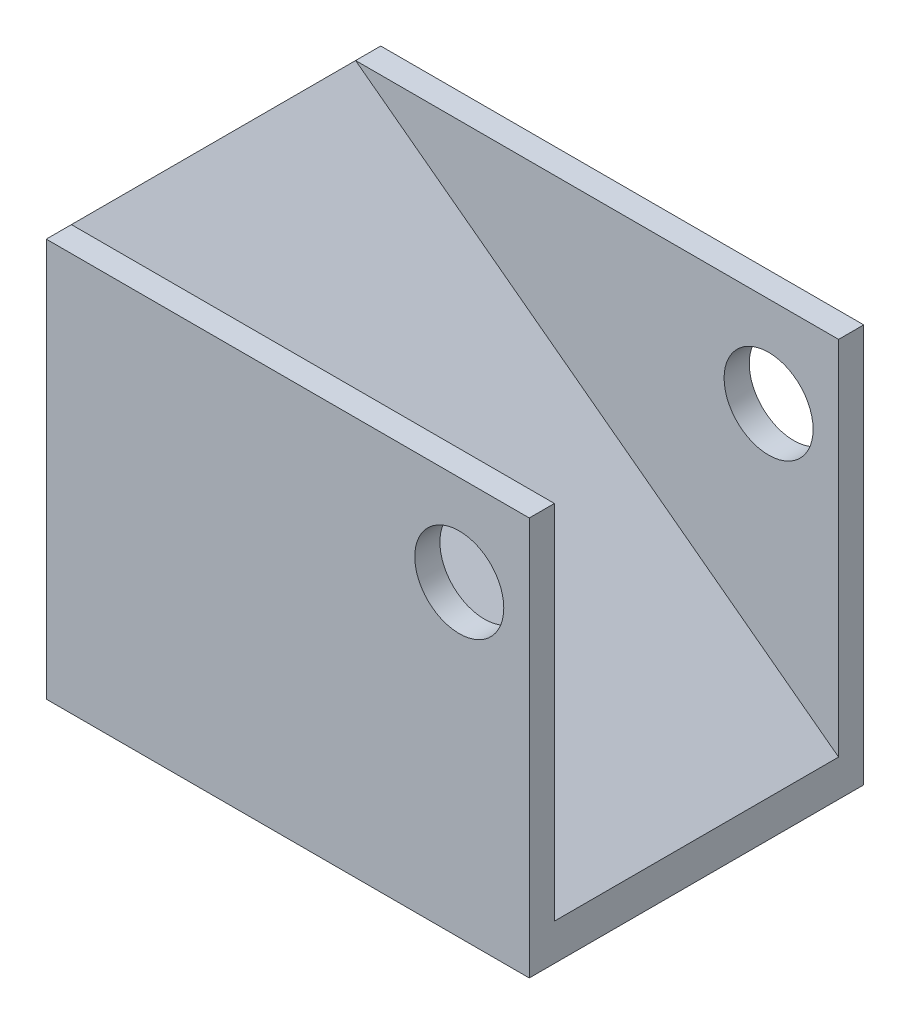
SolidWorks part; units mm, degrees
ref_plane "Front Plane" through (0, 0, 0) normal (0, 0, 1) x (1, 0, 0)
ref_plane "Top Plane" through (0, 0, 0) normal (0, 1, 0) x (1, 0, 0)
ref_plane "Right Plane" through (0, 0, 0) normal (1, 0, 0) x (0, 0, -1)
sketch "Sketch8" plane through (0, 0, 0) normal (0, 1, 0) x (1, 0, 0)
  line L0 (-44.9741, -2.9009) -> (-44.9741, -40.7469)
  line L1 (-44.9741, -40.7469) -> (2.1658, -40.7469)
  line L2 (2.1658, -40.7469) -> (2.1658, -35.808)
  line L3 (2.1658, -2.9009) -> (-44.9741, -2.9009)
  line L4 (2.1658, -7.8398) -> (6.7556, -12.4295)
  line L5 (2.1658, -7.8398) -> (2.1658, -2.9009)
  line L6 (6.7556, -31.2182) -> (2.1658, -35.808)
  line L7 (6.7556, -12.4295) -> (33.8879, -12.4295)
  line L8 (33.8879, -12.4295) -> (33.8879, -31.2182)
  line L9 (33.8879, -31.2182) -> (6.7556, -31.2182)
  line L10 (-44.9741, -21.8239) -> (33.8879, -21.8239) construction
  dimension "D1" = 37.846
  dimension "D2" = 47.1399
  dimension "D3" = 45
  dimension "D4" = 45
  dimension "D5" = 4.5898
  dimension "D6" = 18.923
  dimension "D7" = 4.9389
  dimension "D8" = 78.8619
extrude "Boss-Extrude6" add sketch "Sketch8" along normal blind 2.0599
sketch "Sketch9" plane through (0, 2.0599, 0) normal (0, 1, 0) x (1, 0, 0)
  line L0 (33.8879, -13.8418) -> (6.7556, -13.8418)
  line L1 (33.8879, -31.2182) -> (33.8879, -12.4295) construction
  line L2 (6.7556, -13.8418) -> (6.7556, -12.4295)
  line L3 (6.7556, -12.4295) -> (33.8879, -12.4295)
  line L4 (33.8879, -12.4295) -> (33.8879, -13.8418)
  line L5 (6.7556, -31.2182) -> (6.7556, -29.806)
  line L6 (6.7556, -29.806) -> (33.8879, -29.806)
  line L7 (33.8879, -29.806) -> (33.8879, -31.2182)
  line L8 (33.8879, -31.2182) -> (6.7556, -31.2182)
  dimension "D1" = 1.4122
  dimension "D2" = 1.4122
extrude "Boss-Extrude7" add sketch "Sketch9" along normal blind 20.32
sketch "Sketch10" plane through (0, 0, 31.2182) normal (0, 0, 1) x (1, 0, 0)
  line L0 (6.7556, 0) -> (33.8879, 0) construction
  line L1 (-44.9741, 2.0599) -> (-44.9741, 0) construction
  circle A0 centre (29.9559, 17.2847) radius 2.5006
  dimension "D2" = 74.93
  dimension "D1" = 17.2847
extrude "Cut-Extrude3" cut sketch "Sketch10" against normal blind 25.4
sketch "Sketch14" plane through (0, 0, 13.8418) normal (0, 0, 1) x (1, 0, 0)
  line L0 (6.7556, 22.3799) -> (33.8879, 2.0599)
  line L1 (6.7556, 22.3799) -> (6.7556, 19.8268)
  line L2 (6.7556, 22.3799) -> (6.7556, 2.0599) construction
  line L3 (6.7556, 19.8268) -> (30.5689, 2.0599)
  line L4 (30.5689, 2.0599) -> (33.8879, 2.0599)
extrude "Boss-Extrude10" add sketch "Sketch14" along normal blind 16.0299
sketch "Sketch15" plane through (0, 2.0599, 0) normal (0, 1, 0) x (1, 0, 0)
  line L0 (6.7556, -29.806) -> (6.7556, -13.8418) construction
  line L1 (-44.9741, -40.7469) -> (6.7556, -40.7469)
  line L2 (-44.9741, -40.7469) -> (-44.9741, -2.9009)
  line L3 (-44.9741, -2.9009) -> (6.7556, -2.9009)
  line L4 (6.7556, -40.7469) -> (6.7556, -2.9009)
  line L5 (2.1658, -2.9009) -> (-44.9741, -2.9009) construction
extrude "Cut-Extrude5" cut sketch "Sketch15" against normal through all
ref_plane "Plane2" through (6.7556, 0, 31.2182) normal (1, 0, 0) x (0, 0, -1)
